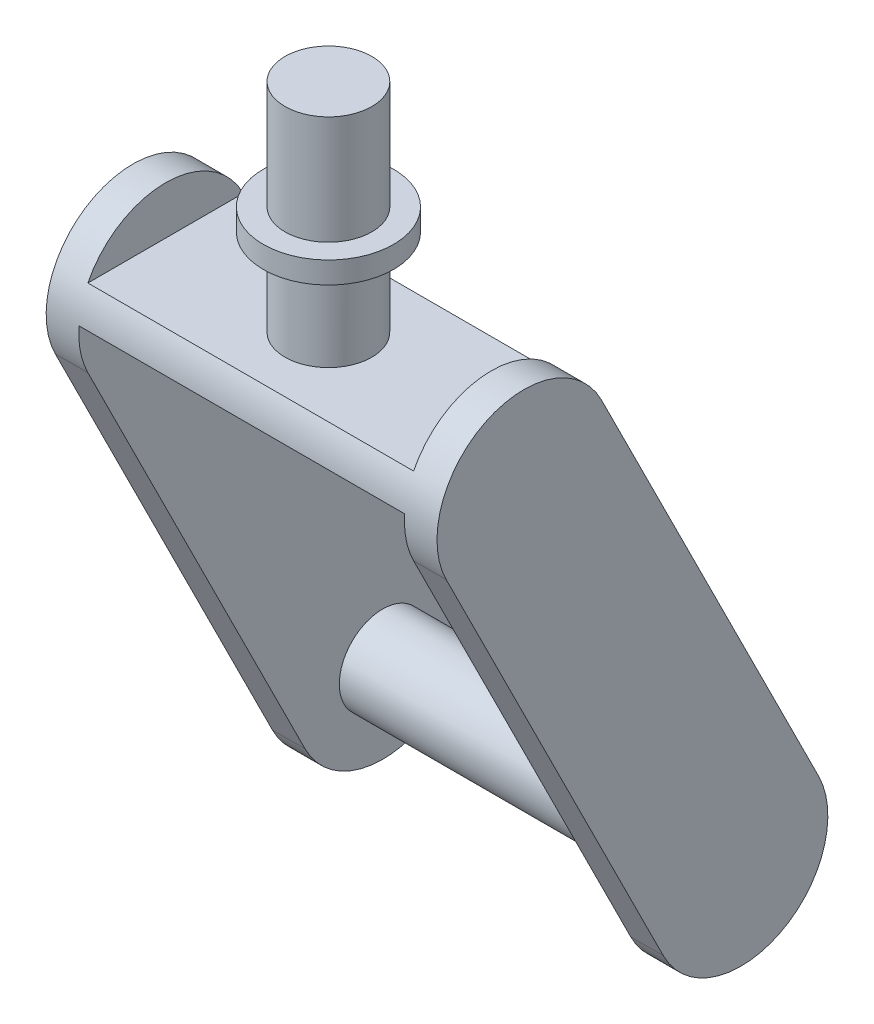
SolidWorks part; units mm, degrees
ref_plane "前视基准面" through (0, 0, 0) normal (0, 0, 1) x (1, 0, 0)
ref_plane "上视基准面" through (0, 0, 0) normal (0, 1, 0) x (1, 0, 0)
ref_plane "右视基准面" through (0, 0, 0) normal (1, 0, 0) x (0, 0, -1)
sketch "草图1" plane through (0, 0, 0) normal (1, 0, 0) x (0, 0, -1)
  circle A0 centre (0, 0) radius 4
extrude "凸台-拉伸1" add sketch "草图1" along normal blind 15 and the other way blind 15
sketch "草图2" plane through (15, 0, 0) normal (1, 0, 0) x (0, 0, -1)
  line L0 (0, 0) -> (-20, 40) construction
  line L1 (0, 0) -> (-20, 0) construction
  line L2 (-20, 40) -> (-20, 0) construction
  line L3 (-27.1554, 36.4223) -> (-7.1554, -3.5777)
  line L4 (-12.8446, 43.5777) -> (7.1554, 3.5777)
  circle A0 centre (0, 0) radius 8
  circle A1 centre (-20, 40) radius 8
  point P10 (-31.031, 38.3394)
  point P11 (-23.3467, 39.2581)
  circle M6 centre (0, 0) radius 4
  dimension "D1" = 16
  dimension "D2" = 16
  dimension "D3" = 20
  dimension "D4" = 40
extrude "凸台-拉伸3" add sketch "草图2" along normal blind 3 contours A1 | M6 | A0 M6 | A1 L3 A0 L4 region at (15, 20, 10) region at (15, 40, 20) region at (15, 6.953, 3.4765) region at (15, 0, 0)
mirror "镜向2" about plane through (0, 0, 0) normal (1, 0, 0) of "凸台-拉伸3"
sketch "草图3" plane through (-15, 0, 0) normal (1, 0, 0) x (0, 0, -1)
  line L0 (-12.8446, 43.5777) -> (-27.1554, 43.5777)
  line L1 (-27.9791, 40.5777) -> (-11.3446, 40.5777)
  line L2 (-12.8446, 43.5777) -> (7.1554, 3.5777) construction
  line L3 (-12.8446, 43.5777) -> (7.1554, 3.5777)
  arc A0 (-12.8446, 43.5777) -> (-27.1554, 36.4223) centre (-20, 40) ccw construction
  arc A1 (-27.1554, 43.5777) -> (-27.9791, 40.5777) centre (-20, 40) ccw
  line M4 (7.1554, 3.5777) -> (-12.8446, 43.5777)
  arc M5 (-12.8446, 43.5777) -> (-27.1554, 36.4223) centre (-20, 40) ccw
  dimension "D1" = 3
extrude "凸台-拉伸4" add sketch "草图3" along normal up to surface (30 mm away) contours L1 L0 M5 M4 region at (-15, 42.0405, 19.8796) up to face at (15, 0, -4)
sketch "草图4" plane through (0, 43.5777, 0) normal (0, 1, 0) x (1, 0, 0)
  line L0 (-15, -20) -> (15, -20) construction
  line L1 (-15, -27.1554) -> (-15, -12.8446) construction
  line L2 (15, -12.8446) -> (15, -27.1554) construction
  circle A0 centre (0, -20) radius 4
extrude "凸台-拉伸5" add sketch "草图4" along normal blind 8
sketch "草图5" plane through (0, 51.5777, 0) normal (0, 1, 0) x (1, 0, 0)
  circle A0 centre (0, -20) radius 6
extrude "凸台-拉伸6" add sketch "草图5" along normal blind 2
sketch "草图6" plane through (0, 53.5777, 0) normal (0, 1, 0) x (1, 0, 0)
  circle A0 centre (0, -20) radius 4
extrude "凸台-拉伸7" add sketch "草图6" along normal blind 10
